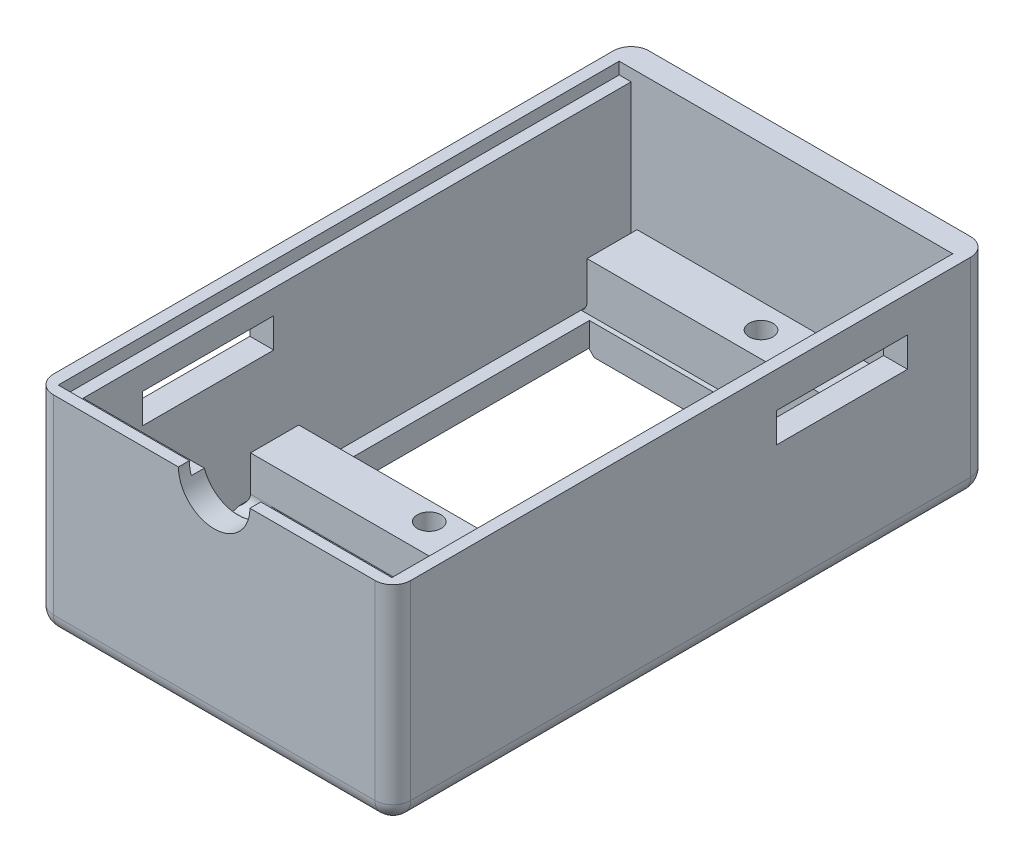
SolidWorks part; units mm, degrees
ref_plane "Front Plane" through (0, 0, 0) normal (0, 0, 1) x (1, 0, 0)
ref_plane "Top Plane" through (0, 0, 0) normal (0, 1, 0) x (1, 0, 0)
ref_plane "Right Plane" through (0, 0, 0) normal (1, 0, 0) x (0, 0, -1)
sketch "Sketch1" plane through (0, 0, 0) normal (0, 1, 0) x (1, 0, 0)
  line L1 (-15, 20) -> (15, 20)
  line L2 (-15, 20) -> (-15, -20)
  line L4 (15, 20) -> (15, -20)
  line L5 (-15, 20) -> (15, -20) construction
  line L6 (-15, -20) -> (15, 20) construction
  line L8 (-15, -20) -> (-15, -30)
  line L9 (-15, -30) -> (15, -30)
  line L10 (15, -20) -> (15, -30)
  point P0 (0, 0)
  dimension "D1" = 40
  dimension "D2" = 30
  dimension "D3" = 10
extrude "Boss-Extrude1" add sketch "Sketch1" along normal blind 17.5
sketch "Sketch2" plane through (0, 17.5, 0) normal (0, 1, 0) x (1, 0, 0)
  line L0 (15, -30) -> (15, 20) construction
  line L1 (-13, 18) -> (13, 18)
  line L2 (-13, 18) -> (-13, -18)
  line L4 (13, 18) -> (13, -18)
  line L5 (-13, 18) -> (13, -18) construction
  line L6 (-13, -18) -> (13, 18) construction
  line L8 (15, 20) -> (-15, 20) construction
  line L9 (-15, 20) -> (-15, -30) construction
  line L12 (-13, -28) -> (13, -28)
  line L13 (13, -28) -> (13, -18)
  line L14 (-13, -18) -> (-13, -28)
  point P0 (0, 0)
  dimension "D1" = 2
  dimension "D3" = 2
  dimension "D4" = 2
extrude "Cut-Extrude1" cut sketch "Sketch2" against normal blind 15.5
sketch "Sketch7" plane through (0, 2, 0) normal (0, 1, 0) x (1, 0, 0)
  line L0 (-12.5, 18) -> (12.5, 18)
  line L1 (-12.5, 18) -> (-12.5, 14)
  line L2 (13, 18) -> (-13, 18) construction
  line L3 (-12.5, 18) -> (12.5, 18)
  line L4 (-12.5, 18) -> (-12.5, -14.45)
  line L5 (-12.5, -14.45) -> (12.5, -14.45)
  line L6 (12.5, 18) -> (12.5, 14)
  line L7 (0, 16.9039) -> (0, 16.9)
  line L9 (-12.5, 14) -> (-12.5, -11)
  line L11 (12.5, 13.4) -> (12.5, -11)
  line L12 (0, -12.95) -> (0, -14.45)
  line L13 (12.5, 14) -> (12.5, 13.4)
  line L15 (-12.5, 18) -> (12.5, 18)
  line L16 (12.5, -11) -> (12.5, -10.4)
  line L17 (11.9, 13.4) -> (-11.9, 13.4)
  line L18 (11.9, -10.4) -> (11.9, 13.4)
  line L19 (-11.9, -11) -> (-11.9, 13.4)
  line L20 (11.9, -10.4) -> (-11.9, -10.4)
  line L21 (12.5, 13.4) -> (12.5, -14.45)
  line L22 (-12.5, 18) -> (-12.5, 13.8)
  line L23 (-12.5, 13.8) -> (12.5, 13.8)
  line L24 (12.5, 18) -> (12.5, 13.8)
  line L25 (-12.5, -14.45) -> (12.5, -14.45)
  line L26 (-12.5, -14.45) -> (-12.5, -10.4)
  line L27 (-12.5, -10.4) -> (12.5, -10.4)
  line L28 (12.5, -14.45) -> (12.5, -10.4)
  circle A0 centre (0, 15.9039) radius 1
  circle A2 centre (0, -11.95) radius 1
  point P3 (0, 18)
  line M3 (13, 18) -> (-13, 18)
  dimension "D6" = 2
  dimension "D11" = 2
  dimension "D1" = 25
  dimension "D2" = 32.45
  dimension "D3" = 4
  dimension "D4" = 25
  dimension "D5" = 1.5
  dimension "D7" = 0.6
  dimension "D8" = 0.6
  dimension "D9" = 0.6
  dimension "D10" = 4.2
  dimension "D12" = 4.05
extrude "Cut-Extrude4" cut sketch "Sketch7" against normal through all contours L20 L18 L17 L19 region at (0, 2, -1.5)
extrude "Boss-Extrude3" add sketch "Sketch7<5>" along normal blind 4 contours L4 L23 L13 L6 L1 A0 M3 | A2 L5 L21 L11 L27 L20 L4 region at (0, 2, -17.7465) region at (-12.2, 2, 10.6533)
sketch "Sketch7<5>" plane through (0, 2, 0) normal (0, 1, 0) x (1, 0, 0) same geometry as "Sketch7"
fillet "Fillet2" radius 1.5 8 edges at (-15, 8.75, -20) (0, 0, -20) (15, 8.75, -20) (15, 0, 5) (-15, 0, 5) (0, 0, 30) (15, 8.75, 30) (-15, 8.75, 30)
sketch "Sketch14" plane through (-13, 0, 0) normal (1, 0, 0) x (0, 0, -1)
  line L8 (-23, 14.5) -> (-12, 14.5)
  line L9 (-23, 14.5) -> (-23, 12)
  line L10 (-23, 12) -> (-12, 12)
  line L11 (-12, 14.5) -> (-12, 12)
  dimension "D2" = 2.5
  dimension "D3" = 11
extrude "Cut-Extrude6" cut sketch "Sketch14" against normal up to next contours L9 L8 L11 L10
sketch "Sketch20" plane through (13, 0, 0) normal (-1, 0, 0) x (0, 0, 1)
  line L0 (-2.1983, 14.5) -> (-2.1983, 11.6313)
  line L4 (-13.1983, 14.5) -> (-2.1983, 14.5)
  line L5 (-13.1983, 14.5) -> (-13.1983, 12)
  line L6 (-13.1983, 12) -> (-2.1983, 12)
  dimension "D3" = 2.5
  dimension "D4" = 11
extrude "Cut-Extrude7" cut sketch "Sketch20" against normal through all contours L5 L6 L0 L4 region at (13, 13.25, -7.6983)
sketch "Sketch21" plane through (0, 0, 0) normal (0, -1, 0) x (1, 0, 0)
  line L0 (11.9, 10.4) -> (12, 10.4)
  line L2 (-12, 17) -> (-12, 10.4)
  line L3 (-12, -17) -> (12, -17)
  line L4 (12, 17) -> (12, 10.4)
  line L5 (-12, 17) -> (-12, 27.5)
  line L6 (13.5, 28.5) -> (-13.5, 28.5) construction
  line L7 (-11.9, 10.4) -> (11.9, 10.4)
  line L9 (-11.9, -13.4) -> (11.9, -13.4)
  line L11 (12, 10.4) -> (-12, 10.4)
  line L12 (-11.9, -13.4) -> (-12, -13.4)
  line L13 (-12, -13.4) -> (12, -13.4)
  line L14 (-12, -13.4) -> (-12, -17)
  line L15 (-12, 27.5) -> (12, 27.5)
  line L16 (12, 27.5) -> (12, 17)
  line L17 (12, -13.4) -> (12, -17)
  point P0 (0, 0)
  line M13 (-11.9, 10.4) -> (11.9, 10.4)
  line M15 (11.9, -13.4) -> (-11.9, -13.4)
  dimension "D1" = 24
  dimension "D2" = 34
  dimension "D3" = 1
extrude "Boss-Extrude4" add sketch "Sketch21" along normal blind 0.5 contours L11 L0 L4 L2 M13 | L17 L13 L12 L14 L3 M15 region at (0, 0, 18.95) region at (0, 0, -15.2)
chamfer "Chamfer2" distance 0.5 angle 45 6 edges at (12, -0.5, 18.95) (-12, -0.5, 18.95) (-12, -0.5, -15.2) (0, -0.5, -17) (12, -0.5, -15.2) (0, -0.5, 27.5)
sketch "Sketch22" plane through (0, 17.5, 0) normal (0, 1, 0) x (1, 0, 0)
  line L0 (-14, -19.0859) -> (-14, -29.0859)
  line L2 (-13, 18) -> (-13, -28)
  line L3 (-13, -28) -> (13, -28)
  line L4 (13, 18) -> (13, -28)
  line L6 (-14, 18) -> (-14, -19.0859)
  line L8 (14, 18) -> (14, -19.0859)
  line L9 (-13.2035, 18) -> (14, -19.0859) construction
  line L10 (-14, -19.0859) -> (13.2035, 18) construction
  line L11 (-14, -29.0859) -> (14, -29.0859)
  line L12 (14, -29.0859) -> (14, -19.0859)
  line L13 (13, 18) -> (14, 18)
  line L14 (14, 18) -> (13, 18)
  line L15 (-13, 18) -> (-14, 18)
  point P6 (0, 0)
  line M11 (13, -28) -> (-13, -28)
  line M12 (-13, -28) -> (-13, 18)
  line M14 (13, 18) -> (13, -28)
  dimension "D2" = 10
extrude "Cut-Extrude8" cut sketch "Sketch22" against normal blind 1 contours L15 L6 L0 L11 L12 L8 L13 M12 M14 M11 region at (-13.4522, 17.5, 0.5429)
sketch "Sketch23" plane through (0, 0, 30) normal (0, 0, 1) x (1, 0, 0)
  line L0 (-13.5, 17.5) -> (13.5, 17.5) construction
  line L1 (-3, 17.5) -> (3, 17.5)
  arc A0 (-3, 17.5) -> (3, 17.5) centre (0, 17.5) ccw
  dimension "D1" = 6
extrude "Cut-Extrude9" cut sketch "Sketch23" against normal up to next
fillet "Fillet3" radius 1 5 edges at (12.5, 2, -15.9) (-12.5, 2, -15.9) (-12.5, 2, 12.425) (12.5, 2, 12.425) (0, 2, 14.45)
